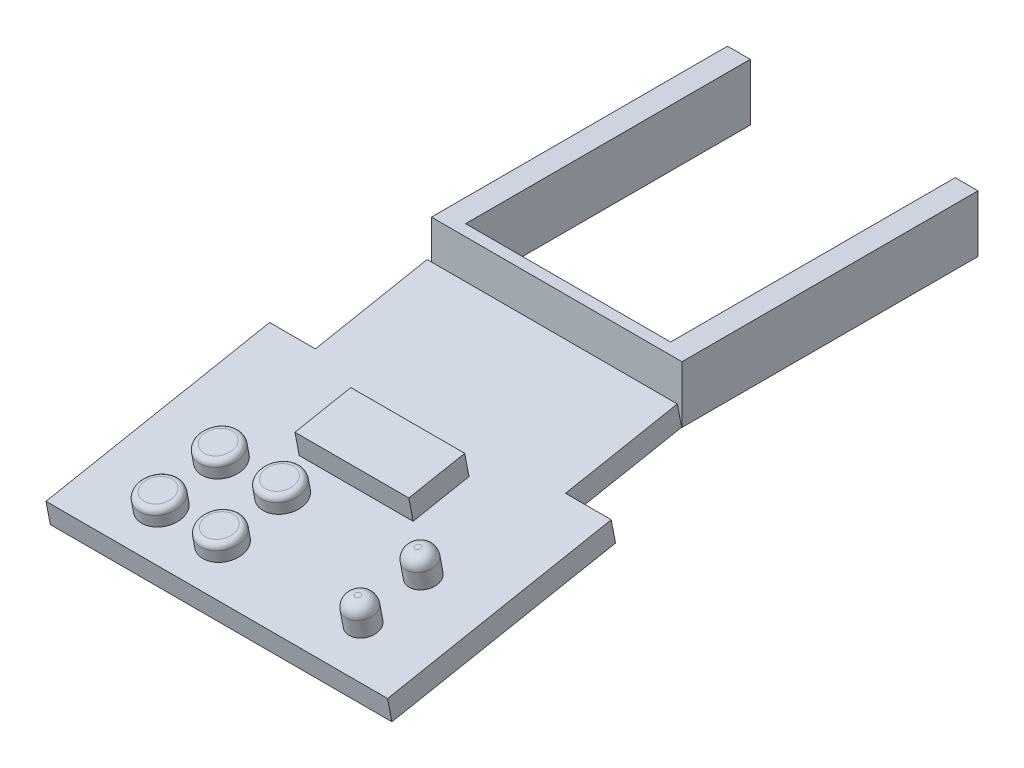
SolidWorks part; units mm, degrees
ref_plane "Front Plane" through (0, 0, 0) normal (0, 0, 1) x (1, 0, 0)
ref_plane "Top Plane" through (0, 0, 0) normal (0, 1, 0) x (1, 0, 0)
ref_plane "Right Plane" through (0, 0, 0) normal (1, 0, 0) x (0, 0, -1)
sketch "Sketch1" plane through (0, 0, 0) normal (0, 1, 0) x (1, 0, 0)
  line L0 (18, 23.2222) -> (22, 23.2222)
  line L1 (-22, 23.2222) -> (-18, 23.2222)
  line L2 (-22, 23.2222) -> (-22, -26.7778)
  line L3 (-22, -26.7778) -> (-18, -26.7778)
  line L4 (-18, 23.2222) -> (-18, -26.7778)
  line L5 (18, 23.2222) -> (18, -26.7778)
  line L6 (18, -26.7778) -> (22, -26.7778)
  line L7 (22, 23.2222) -> (22, -26.7778)
  point P8 (0, 0)
  point P9 (0, 0)
  dimension "D1" = 4
  dimension "D2" = 50
  dimension "D3" = 4
  dimension "D4" = 50
  dimension "D5" = 44
extrude "Boss-Extrude1" add sketch "Sketch1" along normal blind 10
sketch "Sketch2" plane through (0, 0, 26.7778) normal (0, 0, 1) x (1, 0, 0)
  line L1 (-22, 10) -> (22, 10)
  line L2 (-22, 10) -> (-22, 0)
  line L3 (-22, 0) -> (22, 0)
  line L4 (22, 10) -> (22, 0)
extrude "Boss-Extrude2" add sketch "Sketch2" along normal blind 2
ref_plane "Plane1" through (0, 5.3368, 1.0263) normal (0, 0.982, 0.1888) x (1, 0, 0)
sketch "Sketch3" plane through (0, 5.3368, 1.0263) normal (0, 0.982, 0.1888) x (1, 0, 0)
  line L1 (-22, -28.26) -> (21.9437, -28.26)
  line L2 (-22, -28.26) -> (-22, -48.26)
  line L3 (-22, -48.26) -> (21.9437, -48.26)
  line L4 (21.9437, -28.26) -> (21.9437, -48.26)
  line L5 (-30.0281, -48.26) -> (29.9719, -48.26)
  line L6 (-30.0281, -48.26) -> (-30.0281, -88.26)
  line L7 (-30.0281, -88.26) -> (29.9719, -88.26)
  line L8 (29.9719, -48.26) -> (29.9719, -88.26)
  point P9 (-0.0281, -48.26)
  dimension "D1" = 20
  dimension "D2" = 40
  dimension "D3" = 60
  dimension "D4" = 30
extrude "Boss-Extrude3" add sketch "Sketch3" along normal blind 4 separate body contours L4 L1 L2 L3 | L8 L5 L3 L6 L7 region at (-0.0281, -1.8885, 38.5978) region at (-0.0281, -7.5539, 68.058)
sketch "Sketch4" plane through (0, 9.2648, 1.7817) normal (0, 0.982, 0.1888) x (1, 0, 0)
  line L0 (-30.0281, -48.26) -> (-30.0281, -88.26) construction
  line L1 (-10.0281, -53.3275) -> (9.9719, -53.3275)
  line L2 (-10.0281, -53.3275) -> (-10.0281, -63.3275)
  line L3 (-10.0281, -63.3275) -> (9.9719, -63.3275)
  line L4 (9.9719, -53.3275) -> (9.9719, -63.3275)
  circle A0 centre (-17.4526, -69.6913) radius 3.5
  circle A1 centre (-17.4526, -80.449) radius 3.5
  circle A2 centre (-6.6949, -69.6913) radius 3.5
  circle A3 centre (-6.6949, -80.449) radius 3.5
  circle A4 centre (18.0024, -69.6913) radius 2.5
  circle A5 centre (18.0024, -80.449) radius 2.5
  point P4 (-0.0281, -63.3275)
  dimension "D4" = 7
  dimension "D5" = 7
  dimension "D6" = 7
  dimension "D7" = 7
  dimension "D8" = 5
  dimension "D9" = 5
  dimension "D1" = 20
  dimension "D2" = 10
  dimension "D3" = 30
extrude "Boss-Extrude4" add sketch "Sketch4" along normal blind 4 contours L1 L4 L3 L2
extrude "Boss-Extrude5" add sketch "Sketch4<3>" along normal blind 3 contours A2
sketch "Sketch4<3>" plane through (0, 9.2648, 1.7817) normal (0, 0.982, 0.1888) x (1, 0, 0) same geometry as "Sketch4"
extrude "Boss-Extrude6" add sketch "Sketch4<4>" along normal blind 3 contours A0 | A1 | A3
sketch "Sketch4<4>" plane through (0, 9.2648, 1.7817) normal (0, 0.982, 0.1888) x (1, 0, 0) same geometry as "Sketch4"
extrude "Boss-Extrude7" add sketch "Sketch4<5>" along normal blind 5 contours A5 | A4
sketch "Sketch4<5>" plane through (0, 9.2648, 1.7817) normal (0, 0.982, 0.1888) x (1, 0, 0) same geometry as "Sketch4"
fillet "Fillet1" radius 2 2 edges at (18.0024, -1.4898, 84.1824) (18.0024, 0.5417, 73.6183)
fillet "Fillet2" radius 1 4 edges at (-17.4526, -3.6427, 84.7867) (-6.6949, -3.6427, 84.7867) (-6.6949, -1.6111, 74.2226) (-17.4526, -1.6111, 74.2226)
